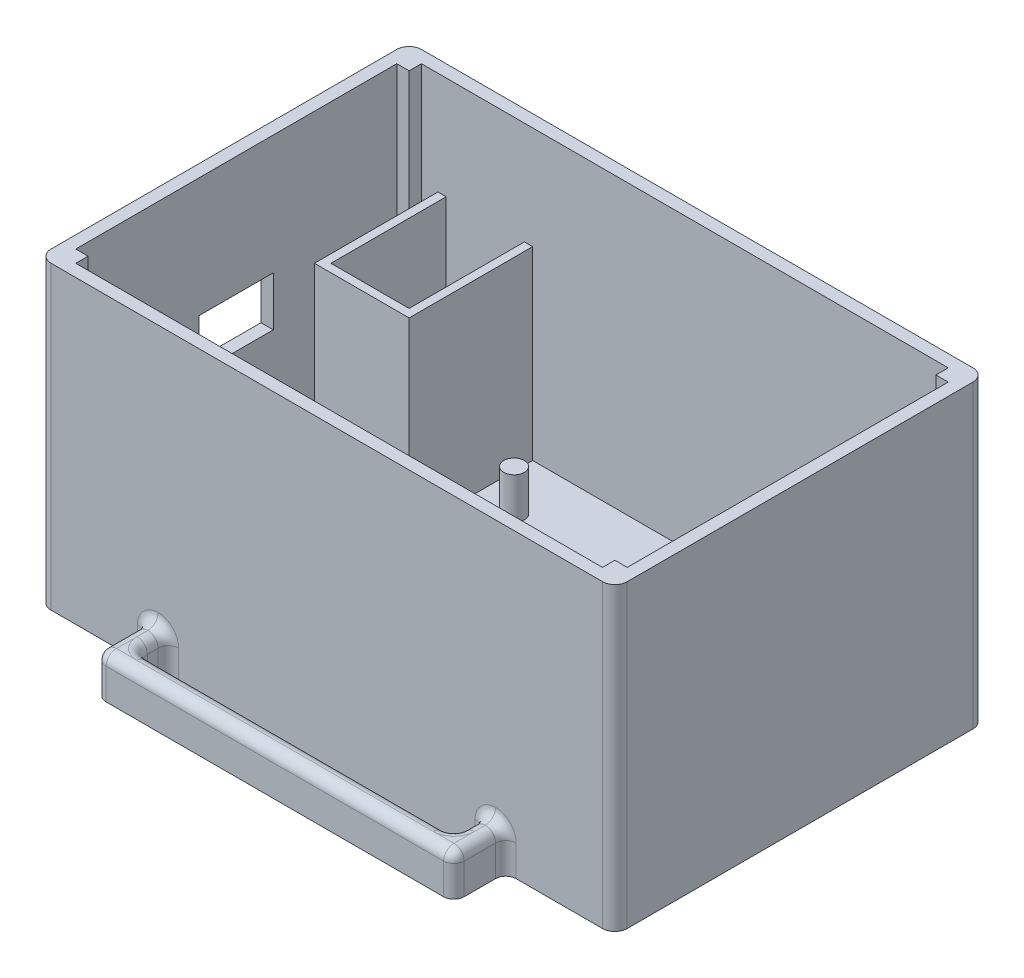
SolidWorks part; units mm, degrees
ref_plane "Piano frontale" through (0, 0, 0) normal (0, 0, 1) x (1, 0, 0)
ref_plane "Piano superiore" through (0, 0, 0) normal (0, 1, 0) x (1, 0, 0)
ref_plane "Piano destro" through (0, 0, 0) normal (1, 0, 0) x (0, 0, -1)
sketch "Schizzo2" plane through (0, 0, 0) normal (0, 1, 0) x (1, 0, 0)
  line L1 (-22.3395, 77.0475) -> (111.6605, 77.0475)
  line L2 (-25.3395, 74.0475) -> (-25.3395, -9.9525)
  line L3 (-22.3395, -12.9525) -> (111.6605, -12.9525)
  line L4 (114.6605, 74.0475) -> (114.6605, -9.9525)
  line L18 (-22.3395, 71.0475) -> (-19.3395, 71.0475)
  line L19 (-19.3395, 71.0475) -> (-19.3395, 74.0475)
  line L20 (-25.3395, 32.0475) -> (114.6605, 32.0475) construction
  line L22 (-2.8395, 77.0475) -> (2.1605, 77.0475)
  line L26 (82.1605, 77.0475) -> (87.1605, 77.0475)
  line L29 (108.6605, 74.0475) -> (108.6605, 71.0475)
  line L30 (-19.3395, 74.0475) -> (108.6605, 74.0475)
  line L31 (-22.3395, 71.0475) -> (-22.3395, -6.9525)
  line L32 (-19.3395, -9.9525) -> (108.6605, -9.9525)
  line L33 (111.6605, 71.0475) -> (111.6605, -6.9525)
  line L34 (108.6605, 71.0475) -> (111.6605, 71.0475)
  line L35 (108.6605, -9.9525) -> (108.6605, -6.9525)
  line L36 (108.6605, -6.9525) -> (111.6605, -6.9525)
  line L37 (-22.3395, -6.9525) -> (-19.3395, -6.9525)
  line L38 (-19.3395, -6.9525) -> (-19.3395, -9.9525)
  arc A4 (-25.3395, -9.9525) -> (-22.3395, -12.9525) centre (-22.3395, -9.9525) ccw
  arc A5 (114.6605, -9.9525) -> (111.6605, -12.9525) centre (111.6605, -9.9525) cw
  arc A6 (111.6605, 77.0475) -> (114.6605, 74.0475) centre (111.6605, 74.0475) cw
  arc A7 (-22.3395, 77.0475) -> (-25.3395, 74.0475) centre (-22.3395, 74.0475) ccw
  point P24 (-25.3395, -12.9525)
  point P27 (114.6605, -12.9525)
  point P34 (-25.3395, 77.0475)
  point P36 (44.6605, 74.0475)
  point P37 (44.6605, 77.0475)
  point P38 (111.6605, 32.0475)
  dimension "D1" = 140
  dimension "D2" = 90
  dimension "D7" = 3
  dimension "D8" = 3
extrude "Corpo centrale" add sketch "Schizzo2" along normal blind 70 contours L20 L2 L3 L4 L33 L32 L31 | L2 L20 L31 L30 L33 L4 L1
sketch "Schizzo13" plane through (-25.3395, 0, 0) normal (-1, 0, 0) x (0, 0, 1)
  line L0 (-41.0475, 41) -> (-41.0475, 29)
  line L2 (-41.0475, 29) -> (-23.0475, 29)
  line L3 (-23.0475, 29) -> (-23.0475, 41)
  line L4 (-23.0475, 41) -> (-41.0475, 41)
  line L7 (-74.0475, 70) -> (9.9525, 70) construction
  line L10 (9.9525, 70) -> (9.9525, 0) construction
  point P6 (-32.0475, 70)
  point P7 (-32.0475, 41)
  point P15 (9.9525, 35)
  point P16 (-23.0475, 35)
  dimension "D1" = 12
  dimension "D2" = 18
extrude "On/off" cut sketch "Schizzo13" against normal up to surface (3 mm away) up to face at (-22.3395, 35, -32.0475)
sketch "Schizzo18" plane through (0, 0, 0) normal (0, -1, 0) x (1, 0, 0)
  line L0 (-25.3395, 9.9525) -> (-25.3395, -74.0475)
  line L1 (-22.3395, -77.0475) -> (111.6605, -77.0475)
  line L2 (114.6605, -74.0475) -> (114.6605, 9.9525)
  line L3 (111.6605, 12.9525) -> (-22.3395, 12.9525)
  line L4 (-22.3395, 12.9525) -> (111.6605, 12.9525) construction
  line L5 (-25.3395, -74.0475) -> (-25.3395, 9.9525) construction
  line L6 (-22.3395, -77.0475) -> (111.6605, -77.0475) construction
  arc A0 (-25.3395, -74.0475) -> (-22.3395, -77.0475) centre (-22.3395, -74.0475) ccw
  arc A1 (114.6605, -74.0475) -> (111.6605, -77.0475) centre (111.6605, -74.0475) cw
  arc A2 (111.6605, 12.9525) -> (114.6605, 9.9525) centre (111.6605, 9.9525) cw
  arc A3 (-22.3395, 12.9525) -> (-25.3395, 9.9525) centre (-22.3395, 9.9525) ccw
  point P10 (-25.3395, -77.0475)
  point P13 (114.6605, -77.0475)
  point P16 (114.6605, 12.9525)
  point P19 (-25.3395, 12.9525)
extrude "Fondo" add sketch "Schizzo18" along normal blind 3
ref_plane "Piano2" through (0, 0, -32.0475) normal (0, 0, 1) x (1, 0, 0)
sketch "Footprint PCB" plane through (0, 0, 0) normal (0, 1, 0) x (1, 0, 0)
  line L0 (9.1605, 68.0475) -> (9.1605, -3.9525)
  line L4 (107.1605, -3.9525) -> (107.1605, 68.0475)
  line L5 (-17.8395, 68.0475) -> (107.1605, 68.0475)
  line L6 (-17.8395, -3.9525) -> (-17.8395, 68.0475)
  line L7 (-17.8395, -3.9525) -> (107.1605, -3.9525)
  line L9 (108.6605, 74.0475) -> (-19.3395, 74.0475)
  line L10 (-22.3395, 71.0475) -> (-22.3395, -6.9525)
  line L11 (-19.3395, -9.9525) -> (108.6605, -9.9525)
  line L12 (111.6605, -6.9525) -> (111.6605, 71.0475)
  line L18 (-22.3395, 71.0475) -> (-22.3395, -6.9525)
  line L19 (-19.3395, -9.9525) -> (108.6605, -9.9525)
  line L24 (-19.3395, 71.0475) -> (-22.3395, 71.0475)
  line L25 (-19.3395, 71.0475) -> (-22.3395, 71.0475)
  line L26 (-19.3395, 74.0475) -> (-19.3395, 71.0475)
  line L27 (-19.3395, 74.0475) -> (-19.3395, 71.0475)
  line L29 (111.6605, -6.9525) -> (111.6605, 71.0475)
  line L30 (108.6605, 74.0475) -> (-19.3395, 74.0475)
  line L39 (-22.3395, -6.9525) -> (-19.3395, -6.9525)
  line L40 (-22.3395, -6.9525) -> (-19.3395, -6.9525)
  line L41 (-19.3395, -6.9525) -> (-19.3395, -9.9525)
  line L42 (-19.3395, -6.9525) -> (-19.3395, -9.9525)
  line L43 (108.6605, -9.9525) -> (108.6605, -6.9525)
  line L44 (108.6605, -9.9525) -> (108.6605, -6.9525)
  line L45 (108.6605, -6.9525) -> (111.6605, -6.9525)
  line L46 (108.6605, -6.9525) -> (111.6605, -6.9525)
  line L47 (111.6605, 71.0475) -> (108.6605, 71.0475)
  line L48 (111.6605, 71.0475) -> (108.6605, 71.0475)
  line L49 (108.6605, 71.0475) -> (108.6605, 74.0475)
  line L50 (108.6605, 71.0475) -> (108.6605, 74.0475)
  point P7 (9.1605, 68.0475)
  dimension "D2" = 98
  dimension "D1" = 0
sketch "Schizzo23" plane through (0, -3, 0) normal (0, -1, 0) x (1, 0, 0)
  line L0 (1.1605, 12.9525) -> (1.1605, 23.0724)
  line L1 (111.6605, 12.9525) -> (-22.3395, 12.9525) construction
  line L2 (3.6605, 25.5724) -> (85.6605, 25.5724)
  line L3 (88.1605, 23.0724) -> (88.1605, 12.9525)
  line L4 (88.1605, 12.9525) -> (83.1605, 12.9525)
  line L5 (83.1605, 12.9525) -> (83.1605, 18.0724)
  line L6 (80.6605, 20.5724) -> (8.6605, 20.5724)
  line L7 (6.1605, 18.0724) -> (6.1605, 12.9525)
  line L8 (6.1605, 12.9525) -> (1.1605, 12.9525)
  arc A0 (8.6605, 20.5724) -> (6.1605, 18.0724) centre (8.6605, 18.0724) ccw
  arc A1 (83.1605, 18.0724) -> (80.6605, 20.5724) centre (80.6605, 18.0724) ccw
  arc A2 (85.6605, 25.5724) -> (88.1605, 23.0724) centre (85.6605, 23.0724) cw
  arc A3 (1.1605, 23.0724) -> (3.6605, 25.5724) centre (3.6605, 23.0724) cw
  point P21 (44.6605, 20.5724)
  point P22 (44.6605, 25.5724)
  dimension "D1" = 2.5
  dimension "D2" = 2.5
  dimension "D3" = 2.5
  dimension "D4" = 2.5
  dimension "D5" = 5
  dimension "D6" = 5
  dimension "D7" = 72
extrude "Maniglia 1" add sketch "Schizzo23" against normal blind 10
mirror "Maniglia 2" about plane through (0, 0, -32.0475) normal (0, 0, 1) of "Maniglia 1"
fillet "Raccordo55" radius 2.5 5 edges at (1.1605, 7, 18.0125) (1.8927, 7, 24.8402) (44.6605, 7, 25.5724) (87.4283, 7, 24.8402) (88.1605, 7, 18.0125)
fillet "Raccordo56" radius 2.5 7 edges at (84.4105, 7, 12.9525) (83.1605, 7, 15.5125) (82.4283, 7, 19.8402) (44.6605, 7, 20.5724) (6.8927, 7, 19.8402) (6.1605, 7, 15.5125) (4.9105, 7, 12.9525)
fillet "Raccordo57" radius 2.5 4 edges at (1.1605, 0.75, 12.9525) (1.8927, 6.2678, 12.9525) (6.1605, 0.75, 12.9525) (5.4283, 6.2678, 12.9525)
fillet "Raccordo58" radius 2.5 4 edges at (88.1605, 0.75, 12.9525) (87.4283, 6.2678, 12.9525) (83.1605, 0.75, 12.9525) (83.8927, 6.2678, 12.9525)
fillet "Raccordo62" radius 2.5 5 edges at (88.1605, 7, -82.1074) (87.4283, 7, -88.9352) (44.6605, 7, -89.6674) (1.8927, 7, -88.9352) (1.1605, 7, -82.1074)
fillet "Raccordo63" radius 2.5 7 edges at (6.1605, 7, -79.6074) (6.8927, 7, -83.9352) (44.6605, 7, -84.6674) (82.4283, 7, -83.9352) (83.1605, 7, -79.6074) (84.4105, 7, -77.0475) (4.9105, 7, -77.0475)
fillet "Raccordo64" radius 2.5 4 edges at (88.1605, 0.75, -77.0475) (87.4283, 6.2678, -77.0475) (83.1605, 0.75, -77.0475) (83.8927, 6.2678, -77.0475)
fillet "Raccordo65" radius 2.5 4 edges at (1.1605, 0.75, -77.0475) (1.8927, 6.2678, -77.0475) (6.1605, 0.75, -77.0475) (5.4283, 6.2678, -77.0475)
sketch "Schizzo25" plane through (0, 0, 0) normal (0, 1, 0) x (1, 0, 0)
  line L0 (9.1605, 68.0475) -> (9.1605, -3.9525) construction
  line L1 (-17.8395, -3.9525) -> (107.1605, -3.9525) construction
  line L2 (107.1605, -3.9525) -> (107.1605, 68.0475) construction
  line L3 (-17.8395, 68.0475) -> (107.1605, 68.0475) construction
  circle A0 centre (99.6605, 60.5475) radius 2.5
  circle A1 centre (102.6605, 0.5475) radius 2.5
  circle A2 centre (16.6605, 3.5475) radius 2.5
  circle A8 centre (16.6605, 60.5475) radius 2.5
  point P4 (107.1605, -3.9525)
  dimension "D1" = 5
  dimension "D3" = 7.5
  dimension "D4" = 4.5
  dimension "D5" = 4.5
  dimension "D6" = 7.5
  dimension "D7" = 7.5
  dimension "D9" = 7.5
  dimension "D2" = 7.5
  dimension "D10" = 7.5
extrude "Attacco PCB" add sketch "Schizzo25" along normal blind 10
sketch "Schizzo26" plane through (0, 0, 0) normal (0, 1, 0) x (1, 0, 0)
  line L0 (-15.8779, 74.0475) -> (-15.3395, 74.0475)
  line L1 (-19.3395, 74.0475) -> (108.6605, 74.0475) construction
  line L2 (-15.3395, 74.0475) -> (-15.3395, 44.0475)
  line L3 (-15.3395, 44.0475) -> (7.6605, 44.0475)
  line L4 (7.6605, 44.0475) -> (7.6605, 74.0475)
  line L5 (7.6605, 74.0475) -> (5.6605, 74.0475)
  line L6 (5.6605, 74.0475) -> (5.6605, 46.0475)
  line L7 (5.6605, 46.0475) -> (-13.3395, 46.0475)
  line L8 (-13.3395, 46.0475) -> (-13.3395, 74.0475)
  line L9 (-13.3395, 74.0475) -> (-15.8779, 74.0475)
  line L10 (-22.3395, 71.0475) -> (-22.3395, -6.9525) construction
  line M21 (108.6605, 74.0475) -> (-19.3395, 74.0475)
  dimension "D1" = 7
  dimension "D2" = 2
  dimension "D3" = 2
  dimension "D4" = 2
  dimension "D5" = 28
  dimension "D6" = 19
extrude "Case Batteria" add sketch "Schizzo26" along normal blind 45 contours L7 L8 L2 L3 L4 L6 M21
